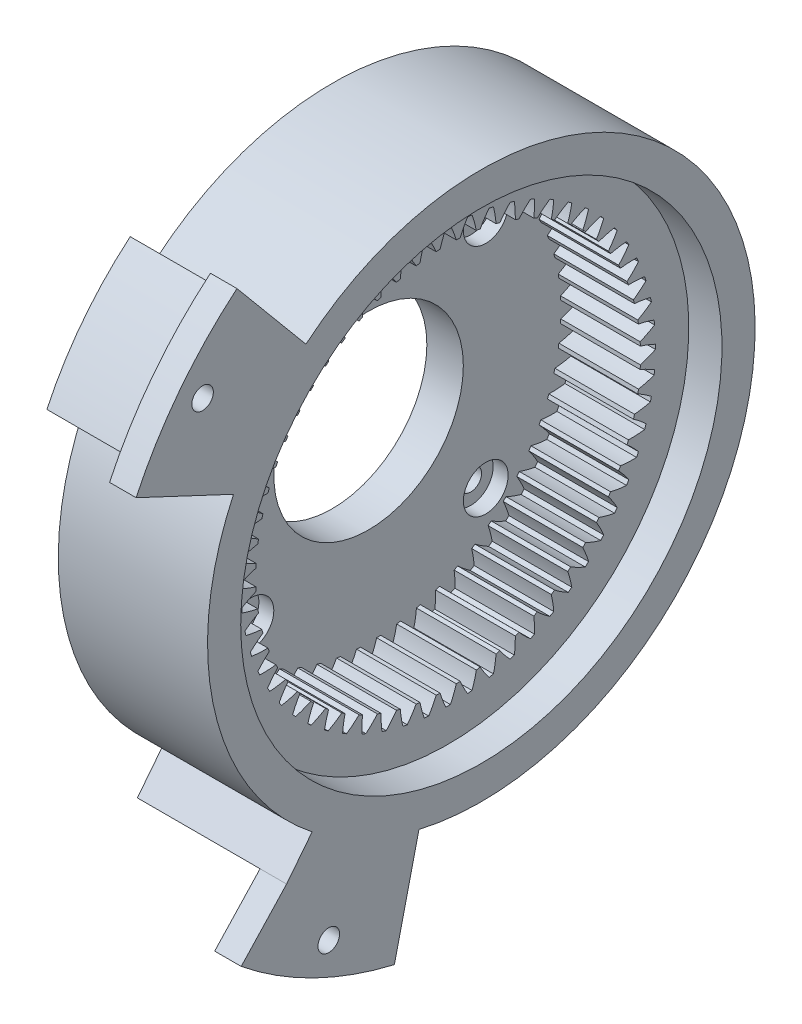
SolidWorks part; units mm, degrees
ref_plane "Plane1" through (0, 0, 0) normal (0, 0, 1) x (1, 0, 0)
ref_plane "Plane2" through (0, 0, 0) normal (0, 1, 0) x (1, 0, 0)
ref_plane "Plane3" through (0, 0, 0) normal (1, 0, 0) x (0, 0, -1)
sketch "HoldingSke" plane through (0, 0, 0) normal (0, 1, 0) x (1, 0, 0)
  line L0 (0, 0) -> (0.5, -0.866)
  line L1 (-15, 0) -> (100, 0) construction
  line L2 (0, 0) -> (-2.1039, 2.3779)
  line L3 (0, 0) -> (-11.863, 4.5341)
  line L4 (0, 0) -> (4.318, 7.479)
  line L5 (0, 0) -> (-23.7986, -8.8762)
  line L6 (0, 0) -> (-10.5278, -7.1032)
  line L7 (-2.1039, 2.3779) -> (3.3635, 27.1825)
  line L8 (-76.2, 3.3779) -> (-54.61, 3.3779)
  line L9 (-71.009, 38.7566) -> (-53.1078, 45.2721)
  line L10 (-76.2, 71.12) -> (104.1128, 71.12)
  line L11 (0, 0) -> (-12, 0)
  line L12 (-76.2, 101.6) -> (-76.162, 101.6)
  line L13 (24.9733, 27.94) -> (52.9518, 28.4284)
  line L14 (24.9733, 27.94) -> (24.9743, 27.94)
  line L15 (24.9733, 27.94) -> (100.4006, 29.5858)
  circle A0 centre (0, 0) radius 12.5
  circle A1 centre (0, 0) radius 12.7
  circle A2 centre (0, 0) radius 12.7
  dimension "MHD" = 25.4
  dimension "Hub_dia" = 25.4
  dimension "Diameter" = 25
  dimension "Num_teeth" = 60
  dimension "Pitch" = 1
  dimension "Overall_len" = 25.4
  dimension "Show_teeth" = 60
  dimension "Thickness" = 12.7
  dimension "OAL" = 25.4001
  dimension "T_dim" = 21.59
  dimension "Ap" = 20
  dimension "H" = 19.05
  dimension "Pitch_radius" = 180.3128
  dimension "Width" = 12
  dimension "Backlash" = 0.038
  dimension "Addendum_fac" = 1
  dimension "Dedendum_fac" = 1.25
  dimension "Clearance_fac" = 0.25
  dimension "Dedendum_add" = 0.001
  dimension "Module" = 1
sketch "BasProSke" plane through (0, 0, 0) normal (0, 1, 0) x (1, 0, 0)
  line L0 (-10, 0) -> (60, 0) construction
  line L1 (0, 29) -> (0, 31.2764)
  line L2 (0, 29) -> (12, 29)
  line L3 (12, 29) -> (12, 31.2764)
  line L4 (12, 31.2764) -> (0, 31.2764)
  dimension "Thickness" = 12
  dimension "Diameter" = 62.5528
  dimension "Inside_diameter" = 58
revolve "Base-Revolve" add sketch "BasProSke" angle 360 about L0
sketch "TooCutSke" plane through (0, 0, 0) normal (1, 0, 0) x (0, 0, -1)
  line L3 (0.8803, 29.9871) -> (0.8803, 53.6633) construction
  line L4 (0, 0) -> (0, 59.563) construction
  line L5 (0, 0) -> (-3.576, 68.2339) construction
  line L6 (-13.1633, 24.7167) -> (36.4631, 27.3175) construction
  circle A0 centre (0, 0) radius 30 construction
  circle A1 centre (0, 0) radius 31.251 construction
  circle A2 centre (0, 0) radius 25.3717 construction
  circle A3 centre (0, 0) radius 28.9746 construction
  arc A4 (1.2274, 28.9486) -> (0.3395, 31.2492) centre (-13.1633, 24.7167) ccw
  arc A5 (1.2274, 28.9486) -> (-1.2274, 28.9486) centre (0, 0) ccw
  arc A6 (0.3395, 31.2492) -> (-0.3395, 31.2492) centre (0, 0) ccw
  arc A7 (-0.3395, 31.2492) -> (-1.2274, 28.9486) centre (13.1633, 24.7167) ccw
  dimension "Pitch_dia" = 60
  dimension "Base_dia" = 50.7434
  dimension "Root_dia" = 62.502
  dimension "Overcut_dia" = 57.9492
  dimension "Flank_rad" = 15
  dimension "Half_ang" = 3
  dimension "Half_CT" = 0.8803
extrude "ToothCut" cut sketch "TooCutSke" along normal through all
fillet "Breaks" [suppressed] radius 0.1
fillet "RootFillets" [suppressed] radius 0.251
pattern_circular "TeethCuts" count 60 every 6 about axis through (-10, 0, 0) along (1, 0, 0) of "RootFillets", "Breaks", "ToothCut"
scale "Scale1" scale about centroid uniform scaling yes scale factor 2
sketch "Sketch1" plane through (18, 0, 0) normal (1, 0, 0) x (0, 0, -1)
  circle A0 centre (0, 0) radius 62.5528
extrude "Extrude-Thin1" add sketch "Sketch1" against normal blind 35 separate body thin thin type one direction wall 10
sketch "Sketch2" plane through (-6, 0, 0) normal (-1, 0, 0) x (0, 0, 1)
  circle A0 centre (0, 0) radius 62.5528
extrude "Boss-Extrude1" add sketch "Sketch2" along normal blind 11
sketch "Sketch6" plane through (-17, 0, 0) normal (-1, 0, 0) x (0, 0, 1)
  circle A0 centre (0, 0) radius 82.5528
  circle A1 centre (0, 0) radius 72.5528
  dimension "D1" = 10
extrude "Boss-Extrude2" add sketch "Sketch6" against normal blind 45 separate body
sketch "Sketch8" plane through (28, 0, 0) normal (1, 0, 0) x (0, 0, -1)
  line L0 (-52.8885, 63.3859) -> (-60.863, 72.9431)
  line L1 (-74.7213, 35.0954) -> (-85.9877, 40.3871)
  line L2 (-51.0218, -64.8979) -> (-58.7148, -74.6832)
  line L3 (-18.8144, -80.3802) -> (-21.6512, -92.4999)
  arc A0 (-60.863, 72.9431) -> (-85.9877, 40.3871) centre (0, 0) ccw
  arc A1 (-52.8885, 63.3859) -> (-74.7213, 35.0954) centre (0, 0) ccw
  circle A2 centre (0, 0) radius 82.5528 construction
  arc A3 (-58.7148, -74.6832) -> (-21.6512, -92.4999) centre (0, 0) ccw
  arc A4 (-51.0218, -64.8979) -> (-18.8144, -80.3802) centre (0, 0) ccw
  dimension "D1" = 190
  dimension "D2" = 25
  dimension "D3" = 25
  dimension "D4" = 101.985
extrude "Boss-Extrude3" add sketch "Sketch8" against normal through all
sketch "Sketch9" plane through (28, 0, 0) normal (1, 0, 0) x (0, 0, -1)
  line L1 (-85.9877, 40.3871) -> (-104.0904, 48.8896)
  line L5 (-60.863, 72.9431) -> (-73.6763, 88.2995)
  line L7 (-51.0218, -64.8979) -> (-58.7148, -74.6832) construction
  line L8 (-58.7148, -74.6832) -> (-72.4005, -89.3486)
  line L10 (-21.6512, -92.4999) -> (-26.2093, -111.9735)
  arc A0 (-73.6763, 88.2995) -> (-104.0904, 48.8896) centre (0, 0) ccw
  arc A1 (-58.7148, -74.6832) -> (-21.6512, -92.4999) centre (0, 0) ccw construction
  arc A2 (-60.863, 72.9431) -> (-85.9877, 40.3871) centre (0, 0) ccw
  arc A3 (-72.4005, -89.3486) -> (-26.2093, -111.9735) centre (0, 0) ccw
  arc A4 (-58.7148, -74.6832) -> (-21.6512, -92.4999) centre (0, 0) ccw
extrude "Boss-Extrude4" add sketch "Sketch9" against normal blind 8
scale "Scale2" scale about centroid uniform scaling yes scale factor 0.666667
sketch "Sketch20" plane through (-3.7474, 0, 0) normal (1, 0, 0) x (0, 0, -1)
  line L1 (21.663, -24.0026) -> (-25.437, -24.0026) construction
  line L2 (21.663, -24.0026) -> (21.663, 23.0974) construction
  line L3 (21.663, 23.0974) -> (-25.437, 23.0974) construction
  line L4 (-25.437, -24.0026) -> (-25.437, 23.0974) construction
  line L5 (21.663, -24.0026) -> (-25.437, 23.0974) construction
  line L6 (21.663, 23.0974) -> (-25.437, -24.0026) construction
  circle A0 centre (-1.887, -0.4526) radius 19.05
  arc A1 (-51.7012, 22.9444) -> (-35.9015, -43.7179) centre (-1.887, -0.4526) ccw construction
  circle A2 centre (21.663, 23.0974) radius 2.165
  circle A3 centre (-25.437, 23.0974) radius 2.165
  circle A4 centre (-25.437, -24.0026) radius 2.165
  circle A5 centre (21.663, -24.0026) radius 2.165
  dimension "D1" = 38.1
  dimension "D3" = 4.33
  dimension "D2" = 47.1
extrude "Cut-Extrude6" cut sketch "Sketch20" against normal through all
sketch "Sketch21" plane through (-3.7474, 0, 0) normal (1, 0, 0) x (0, 0, -1)
  circle A0 centre (-25.437, 23.0974) radius 4.5
  circle A1 centre (-25.437, -24.0026) radius 4.5
  circle A2 centre (21.663, -24.0026) radius 4.5
  circle A3 centre (21.663, 23.0974) radius 4.5
  dimension "D1" = 9
extrude "Cut-Extrude7" cut sketch "Sketch21" against normal blind 3
sketch "Sketch23" plane through (18.9192, 0, 0) normal (1, 0, 0) x (0, 0, -1)
  line L0 (-1.887, -0.4526) -> (-57.9195, 42.7898) construction
  line L1 (-1.887, -0.4526) -> (-32.5515, -64.2431) construction
  line L2 (-71.2806, 32.1405) -> (-51.7012, 22.9444) construction
  line L3 (-19.3599, -75.1016) -> (-14.4299, -54.0394) construction
  circle A2 centre (-1.887, -0.4526) radius 35.1415 construction
  arc A3 (-14.4299, -54.0394) -> (-37.146, 41.8046) centre (-1.887, -0.4526) ccw construction
  dimension "D1" = 70.7781
  dimension "D2" = 12.5
  dimension "D3" = 12.5
hole_wizard "Ø1.0mm Dowel Hole2" positions "3DSketch2" profile "Sketch25" hole size "Ø1.0" standard "ANSI Metric" end condition through all
sketch3d "3DSketch2"
  point P0 (18.9192, 42.7898, 57.9195)
  point P3 (18.9192, -64.2431, 32.5515)
sketch "Sketch25" plane through (18.9192, 42.7898, 57.9195) normal (0, 1, 0) x (0, 0, -1)
  line L0 (0, 0) -> (0, 30)
  line L1 (0, 30) -> (2.165, 30)
  line L2 (2.165, 30) -> (2.165, 0)
  line L5 (2.165, 0) -> (0, 0)
  line L11 (0, -6.35) -> (0, 107.95) construction
  dimension "Thru Hole Dia." = 4.33
  dimension "Thru Hole Depth" = 30
equation "' \"Module@HoldingSke\" = 6.35"
equation "' \"Num_teeth@HoldingSke\" = 24"
equation "' \"Ap@HoldingSke\" =  14.5"
equation "' \"Ap@HoldingSke\" = 14.5"
equation "' \"Width@HoldingSke\" = 12"
equation "' \"Diameter@HoldingSke\" = 8 * 25.4"
equation "' \"Show_teeth@HoldingSke\" = 100"
equation "' \"Backlash@HoldingSke\" = 0.009 * 25.4"
equation "' \"Addendum_fac@HoldingSke\" = 1.0"
equation "' \"Dedendum_fac@HoldingSke\" = 1.25"
equation "' \"Dedendum_add@HoldingSke\" = 0.00005 * 25.4"
equation "' \"Clearance_fac@HoldingSke\" = 0.25"
equation "\"Pitch@HoldingSke\" = 1 / \"Module@HoldingSke\" "
equation "\"Overcut_dia@TooCutSke\" = (\"Num_teeth@HoldingSke\" - 2 * \"Addendum_fac@HoldingSke\") / \"Pitch@HoldingSke\" - 0.002 * 25.4"
equation "\"Pitch_dia@TooCutSke\" = \"Num_teeth@HoldingSke\" / \"Pitch@HoldingSke\""
equation "\"Base_dia@TooCutSke\" = \"Num_teeth@HoldingSke\" / \"Pitch@HoldingSke\" * cos((\"Ap@HoldingSke\"  * 3.14159265 / 180)) * 0.90"
equation "\"Root_dia@TooCutSke\" = \"Num_teeth@HoldingSke\"  / \"Pitch@HoldingSke\" + 2 *  \"Dedendum_fac@HoldingSke\"/ \"Pitch@HoldingSke\" + \"Dedendum_add@HoldingSke\" * 2"
equation "\"Half_ang@TooCutSke\" = 180 / \"Num_teeth@HoldingSke\""
equation "\"Half_CT@TooCutSke\" = \"Num_teeth@HoldingSke\" / \"Pitch@HoldingSke\" * sin((3.14159265 / 2 / \"Num_teeth@HoldingSke\")) / 2 + 10 * \"Backlash@HoldingSke\" / 4"
equation "\"Flank_rad@TooCutSke\" = \"Num_teeth@HoldingSke\" / \"Pitch@HoldingSke\" / 4"
equation "\"Radius@RootFillets\"= \"Clearance_fac@HoldingSke\" / \"Pitch@HoldingSke\" + \"Dedendum_add@HoldingSke\""
equation "\"Break_rad@Breaks\" = 0.02 / \"Pitch@HoldingSke\" * 5"
equation "\"Num_teeth@TeethCuts\" = int( \"Show_teeth@HoldingSke\" ) + 1"
equation "\"Num_teeth@TeethCuts\" = ((sgn( \"Num_teeth@TeethCuts\" - \"Num_teeth@HoldingSke\" )-1)*( \"Num_teeth@TeethCuts\" - \"Num_teeth@HoldingSke\" ))/-2+ \"Num_teeth@HoldingSke\""
equation "\"Num_teeth@TeethCuts\" = ((sgn( \"Num_teeth@TeethCuts\" - 2.0)+1)*( \"Num_teeth@TeethCuts\" - 2.0))/2 +2.0"
equation "\"Angle@TeethCuts\" = 360.0 / \"Num_teeth@HoldingSke\""
equation "\"Diameter@BasProSke\" = \"Num_teeth@HoldingSke\"  / \"Pitch@HoldingSke\" + 2 *  \"Dedendum_fac@HoldingSke\"/ \"Pitch@HoldingSke\" + \"Dedendum_add@HoldingSke\" * 2 + 0.002 * 25.4"
equation "\"Diameter@BasProSke\" = ((sgn( \"Diameter@BasProSke\"  - \"Diameter@HoldingSke\" )+1)*( \"Diameter@BasProSke\"  - \"Diameter@HoldingSke\" ))/2 + \"Diameter@HoldingSke\""
equation "\"Inside_diameter@BasProSke\" =  (\"Num_teeth@HoldingSke\" - 2 * \"Addendum_fac@HoldingSke\") / \"Pitch@HoldingSke\" "
equation "\"Thickness@BasProSke\"  = \"Width@HoldingSke\""
